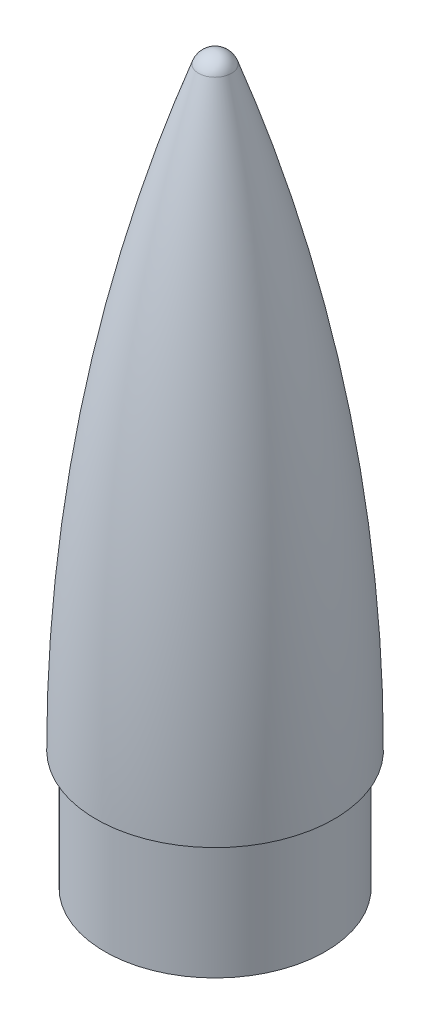
SolidWorks part; units mm, degrees
material "PLA"
ref_plane "Front Plane" through (0, 0, 0) normal (0, 0, 1) x (1, 0, 0)
ref_plane "Top Plane" through (0, 0, 0) normal (0, 1, 0) x (1, 0, 0)
ref_plane "Right Plane" through (0, 0, 0) normal (1, 0, 0) x (0, 0, -1)
sketch "Sketch1" plane through (0, 0, 0) normal (0, 0, 1) x (1, 0, 0)
  line L0 (-20.5, 0) -> (-20.5, -8.881) construction
  line L1 (-19, 0) -> (-20.5, 0)
  line L2 (0, 0) -> (0, 104.3744)
  line L3 (0, 110) -> (-20.5, 110)
  line L4 (-20.5, 0) -> (-20.5, 110)
  line L6 (0, 0) -> (0, -20.5)
  line L7 (0, -20.5) -> (-19, -20.5)
  line L8 (-19, 0) -> (-19, -20.5)
  line L9 (-17, 2) -> (-17, -20.5)
  line L10 (-17, 2) -> (-18.4934, 2)
  arc A0 (-20.5, 0) -> (-2.8264, 102.3802) centre (284.872, 0) cw
  arc A1 (0, 104.3744) -> (-2.8264, 102.3802) centre (0, 101.3744) ccw
  arc A2 (-18.4934, 2) -> (-0.9421, 101.7097) centre (284.872, 0) cw
  arc A3 (0, 102.3744) -> (-0.9421, 101.7097) centre (0, 101.3744) ccw
  dimension "D5" = 6
  dimension "D1" = 110
  dimension "D2" = 20.5
  dimension "D3" = 20.5
  dimension "D4" = 1.5
  dimension "D6" = 2
revolve "Revolve3" add sketch "Sketch1" angle 360 about L2 region at (-19.75, 1.2655, 0)
